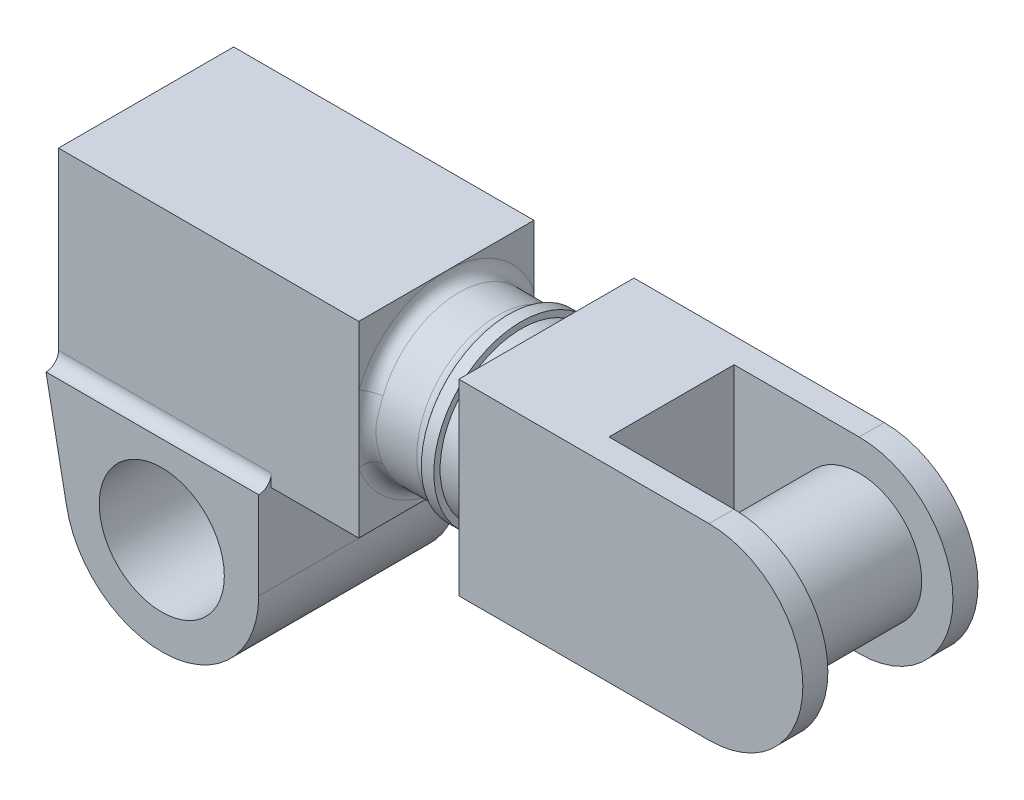
SolidWorks part; units mm, degrees
ref_plane "Front Plane" through (0, 0, 0) normal (0, 0, 1) x (1, 0, 0)
ref_plane "Top Plane" through (0, 0, 0) normal (0, 1, 0) x (1, 0, 0)
ref_plane "Right Plane" through (0, 0, 0) normal (1, 0, 0) x (0, 0, -1)
sketch "Sketch1" plane through (0, 0, 0) normal (1, 0, 0) x (0, 0, -1)
  line L1 (70, -75) -> (-70, -75)
  line L2 (70, -75) -> (70, 75)
  line L3 (70, 75) -> (-70, 75)
  line L4 (-70, -75) -> (-70, 75)
  line L5 (70, -75) -> (-70, 75) construction
  line L6 (70, 75) -> (-70, -75) construction
  point P0 (0, 0)
  dimension "D1" = 150
  dimension "D2" = 140
extrude "Boss-Extrude1" add sketch "Sketch1" along normal blind 240
sketch "Sketch2" plane through (240, 0, 0) normal (1, 0, 0) x (0, 0, -1)
  circle A0 centre (0, 0) radius 65
  dimension "D1" = 130
extrude "Boss-Extrude3" add sketch "Sketch2" along normal blind 50
sketch "Sketch3" plane through (290, 0, 0) normal (1, 0, 0) x (0, 0, -1)
  circle A0 centre (0, 0) radius 70
  dimension "D1" = 140
extrude "Boss-Extrude5" add sketch "Sketch3" along normal blind 10
sketch "Sketch4" plane through (0, 0, 0) normal (0, 0, 1) x (1, 0, 0)
  line L0 (0, -75) -> (16.2188, -158.4383)
  line L1 (240, -75) -> (0, -75) construction
  line L2 (0, 75) -> (0, -75) construction
  line L3 (170.0448, -145) -> (170.0448, -75)
  line L4 (0, -75) -> (170.0448, -75)
  arc A0 (16.2188, -158.4383) -> (170.0448, -145) centre (92.5448, -145) ccw
  circle A1 centre (92.5448, -145) radius 50
  point P12 (92.5448, -142.0244)
  dimension "D1" = 155
  dimension "D2" = 100
  dimension "D3" = 191
  dimension "D4" = 85
  dimension "D5" = 70
extrude "Boss-Extrude6" add sketch "Sketch4" along normal mid plane 160
ref_plane "Plane2" through (0, 0, 10) normal (0, 0, 1) x (1, 0, 0)
sketch "Sketch13" plane through (0, 0, 10) normal (0, 0, 1) x (1, 0, 0)
  point P0 (92.5448, -145)
fillet "Fillet1" radius 10 4 edges at (240, 0, -65) (290, 0, -65) (85.0224, -75, 70) (85.0224, -75, -70)
sketch "Sketch5" plane through (300, 0, 0) normal (1, 0, 0) x (0, 0, -1)
  circle A0 centre (0, 0) radius 65
  dimension "D1" = 130
extrude "Boss-Extrude7" add sketch "Sketch5" along normal blind 20
sketch "Sketch6" plane through (0, 0, 0) normal (0, 0, 1) x (1, 0, 0)
  line L0 (520, 75) -> (320, 75)
  line L1 (320, 75) -> (320, -75)
  line L2 (320, -75) -> (520, -75)
  line L3 (320, -65) -> (320, 65) construction
  arc A0 (520, -75) -> (520, 75) centre (520, 0) ccw
  dimension "D1" = 150
  dimension "D2" = 200
extrude "Boss-Extrude8" add sketch "Sketch6" along normal mid plane 140
ref_plane "Plane1" through (520, 75, 70) normal (-1, 0, 0) x (0, 0, 1)
sketch "Sketch9" plane through (0, 0, 0) normal (0, 0, 1) x (1, 0, 0)
  line L0 (520, 75) -> (420, 75)
  line L3 (420, 75) -> (420, -75)
  line L4 (320, -75) -> (520, -75) construction
  line L5 (420, -75) -> (520, -75)
  arc A2 (520, -75) -> (520, 75) centre (520, 0) ccw construction
  arc A3 (520, -75) -> (520, 75) centre (520, 0) ccw
  dimension "D1" = 100
extrude "Cut-Extrude1" cut sketch "Sketch9" against normal mid plane 100
sketch "Sketch11" plane through (0, 0, -50) normal (0, 0, 1) x (1, 0, 0)
  circle A0 centre (520, 0) radius 50
  dimension "D1" = 100
extrude "Boss-Extrude9" add sketch "Sketch11" along normal blind 100
sketch "Sketch12" plane through (0, 0, -70) normal (0, 0, -1) x (-1, 0, 0)
  text T0 "YASHAR" font "Adobe Gothic Std B" height in points 100
extrude "Boss-Extrude10" add sketch "Sketch12" along normal blind 10
